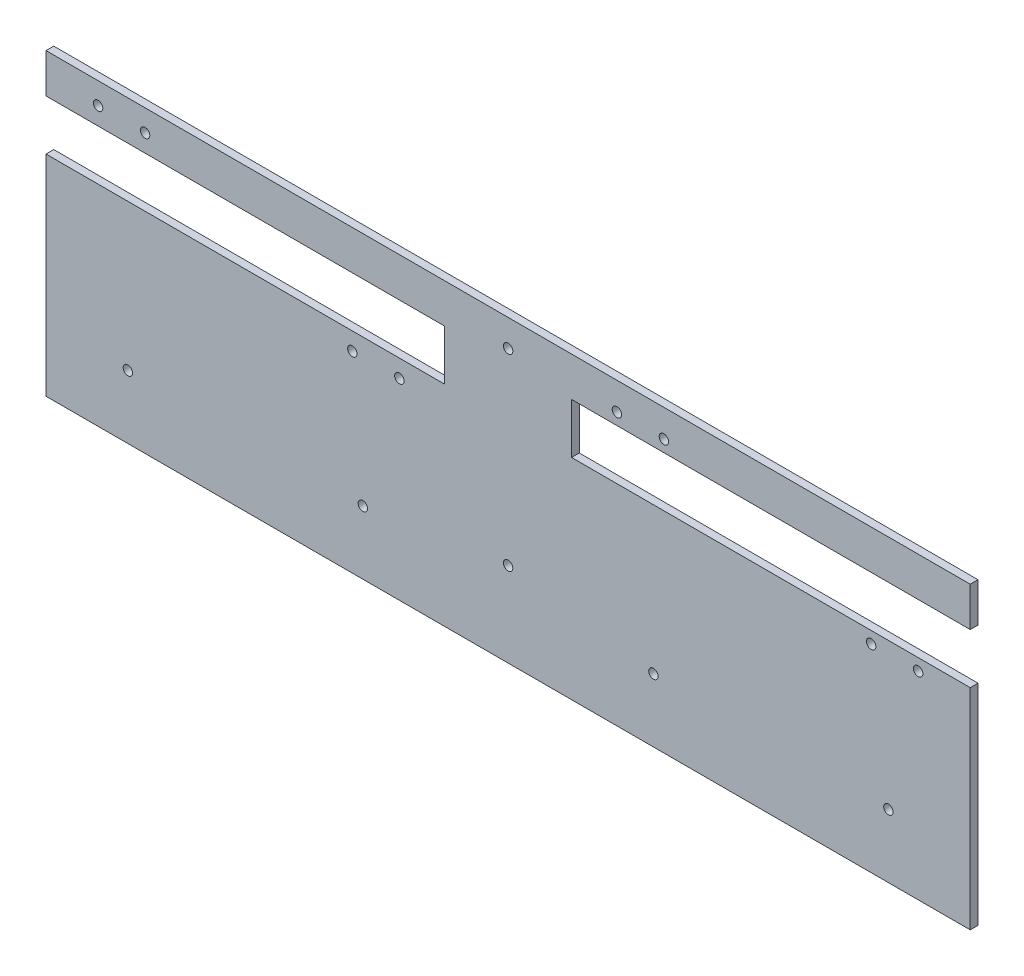
SolidWorks part; units mm, degrees
material "Balsa"
ref_plane "Front Plane" through (0, 0, 0) normal (0, 0, 1) x (1, 0, 0)
ref_plane "Top Plane" through (0, 0, 0) normal (0, 1, 0) x (1, 0, 0)
ref_plane "Right Plane" through (0, 0, 0) normal (1, 0, 0) x (0, 0, -1)
sketch "Sketch1" plane through (0, 0, 0) normal (0, 0, 1) x (1, 0, 0)
  line L1 (223.7, -24.5) -> (-169.7, -24.5)
  line L2 (223.7, -24.5) -> (223.7, 102.9317)
  line L3 (223.7, 102.9317) -> (-169.7, 102.9317)
  line L4 (-169.7, -24.5) -> (-169.7, 102.9317)
  line L5 (223.7, -24.5) -> (-169.7, 102.9317) construction
  line L6 (223.7, 102.9317) -> (-169.7, -24.5) construction
  line L7 (227, -24.5) -> (223.7, -24.5) construction
  line L8 (-173, 102.9317) -> (-169.7, 102.9317) construction
  line L10 (223.7, 144.1231) -> (223.7, -24.5) construction
  line L11 (-169.7, -24.5) -> (-169.7, 144.1269) construction
  point P4 (27, 60.5912)
extrude "Boss-Extrude1" add sketch "Sketch1" along normal up to surface (3.3 mm away)
sketch "Sketch2" plane through (0, 0, 0) normal (0, 0, -1) x (-1, 0, 0)
  line L0 (-223.7, 102.9317) -> (169.7, 102.9317) construction
  line L1 (0, 0) -> (-54, 0)
  line L2 (0, 0) -> (0, 102.9317)
  line L3 (0, 102.9317) -> (-54, 102.9317)
  line L4 (-54, 0) -> (-54, 102.9317)
  line L5 (0, 0) -> (-54, 102.9317) construction
  line L6 (0, 102.9317) -> (-54, 0) construction
  line L7 (-54, 262.7) -> (-54, 0) construction
  line L8 (-27, 0) -> (-27, 102.9317) construction
  line L9 (169.7, 102.9317) -> (169.7, -24.5) construction
  line L10 (-223.7, 29.5) -> (-54, 29.5)
  line L11 (-223.7, 29.5) -> (-223.7, -24.5)
  line L12 (-223.7, -24.5) -> (-54, -24.5)
  line L13 (-54, 29.5) -> (-54, -24.5)
  line L14 (-223.7, 29.5) -> (-54, -24.5) construction
  line L15 (-223.7, -24.5) -> (-54, 29.5) construction
  line L16 (169.7, 29.5) -> (0, 29.5)
  line L17 (169.7, 29.5) -> (169.7, -24.5)
  line L18 (169.7, -24.5) -> (0, -24.5)
  line L19 (0, 29.5) -> (0, -24.5)
  line L20 (169.7, 29.5) -> (0, -24.5) construction
  line L21 (169.7, -24.5) -> (0, 29.5) construction
  line L22 (-223.7, 2.5) -> (169.7, 2.5) construction
  line L23 (-138.85, -24.5) -> (-138.85, 29.5) construction
  circle A0 centre (-27, 11.4659) radius 2
  circle A1 centre (-27, 91.4659) radius 2
  circle A2 centre (-188.85, 2.5) radius 2
  circle A3 centre (-88.85, 2.5) radius 2
  circle A4 centre (34.85, 2.5) radius 2
  circle A5 centre (134.85, 2.5) radius 2
  point P4 (-27, 51.4659)
  point P20 (-138.85, 2.5)
  point P27 (84.85, 2.5)
  dimension "D1" = 4
  dimension "D2" = 4
  dimension "D3" = 40
  dimension "D4" = 40
  dimension "D5" = 4
  dimension "D6" = 50
extrude "Cut-Extrude1" cut sketch "Sketch2" against normal blind 4 contours A1 | A0 | A2 | A3 | A5 | A4
sketch "Sketch3" plane through (0, 0, 0) normal (0, 0, -1) x (-1, 0, 0)
  line L0 (169.7, 102.9317) -> (169.7, -24.5) construction
  line L1 (169.7, 64.8) -> (-223.7, 64.8)
  line L2 (169.7, 64.8) -> (169.7, 86.2)
  line L3 (169.7, 86.2) -> (-223.7, 86.2)
  line L4 (-223.7, 64.8) -> (-223.7, 86.2)
  line L5 (169.7, 64.8) -> (-223.7, 86.2) construction
  line L6 (169.7, 86.2) -> (-223.7, 64.8) construction
  line L7 (-223.7, -24.5) -> (-223.7, 102.9317) construction
  line L8 (35.8344, 64.8) -> (9.0983, 64.8) construction
  line L9 (142.922, 86.2) -> (163.7817, 86.2) construction
  line L10 (0, 64.8) -> (0, 86.2)
  line L11 (-54, 64.8) -> (-54, 86.2)
  line L12 (-54, 262.7) -> (-54, 0) construction
  line L13 (0, 262.7) -> (0, 0) construction
  line L14 (0, 262.7) -> (0, 0) construction
  point P4 (-27, 75.5)
  line M7 (-223.7, 102.9317) -> (-223.7, -24.5)
  line M9 (169.7, -24.5) -> (169.7, 102.9317)
extrude "Cut-Extrude2" cut sketch "Sketch3" against normal blind 6 contours L10 L1 L3 M9 | L1 L11 L3 M7 region at (-84.85, 75.5, 0) region at (138.85, 75.5, 0)
sketch "Sketch4" plane through (0, 0, 3.3) normal (0, 0, 1) x (1, 0, 0)
  circle A0 centre (93.3034, 91.2) radius 2
  circle A1 centre (73.3034, 91.2) radius 2
  circle A2 centre (181.5258, 59.8) radius 2
  circle A3 centre (201.5258, 59.8) radius 2
  circle A4 centre (-127.5258, 93.7) radius 2
  circle A5 centre (-147.5258, 93.7) radius 2
  circle A6 centre (-19.3034, 57.3) radius 2
  circle A7 centre (-39.3034, 57.3) radius 2
  circle A8 centre (-39.3034, 57.3) radius 2 construction
  circle A9 centre (-19.3034, 57.3) radius 2 construction
  circle A10 centre (-127.5258, 93.7) radius 2 construction
  circle A11 centre (-147.5258, 93.7) radius 2 construction
  circle A12 centre (181.5258, 59.8) radius 2 construction
  circle A13 centre (93.3034, 91.2) radius 2 construction
  circle A14 centre (73.3034, 91.2) radius 2 construction
  circle A15 centre (201.5258, 59.8) radius 2 construction
extrude "Cut-Extrude3" cut sketch "Sketch4" against normal through all
